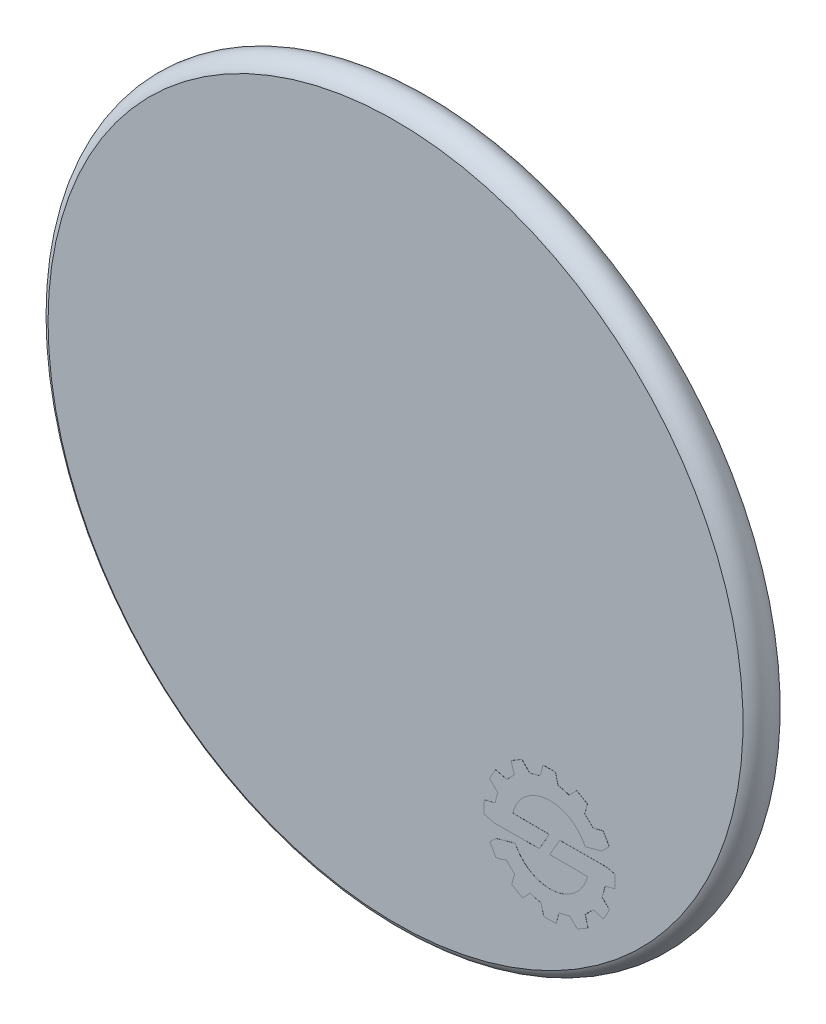
SolidWorks part; units mm, degrees
ref_plane "Front Plane" through (0, 0, 0) normal (0, 0, 1) x (1, 0, 0)
ref_plane "Top Plane" through (0, 0, 0) normal (0, 1, 0) x (1, 0, 0)
ref_plane "Right Plane" through (0, 0, 0) normal (1, 0, 0) x (0, 0, -1)
sketch "Sketch1" plane through (0, 0, 0) normal (0, 1, 0) x (1, 0, 0)
  line L0 (0, 0) -> (-40, 0)
  line L3 (-40, 0) -> (-42, 1.5)
  line L4 (0, 0) -> (0, -3)
  line L5 (0, -3) -> (-42, -3)
  line L6 (-42, -3) -> (-44.5, -3)
  line L8 (-44.5, 1.5) -> (-42, 1.5)
  arc A0 (-44.5, 1.5) -> (-44.5, -3) centre (-43.5625, -0.75) ccw
  dimension "D1" = 40
  dimension "D2" = 42
revolve "Revolve1" add sketch "Sketch1" angle 360 about L4
sketch "Sketch5" plane through (0, 0, 3) normal (0, 0, 1) x (1, 0, 0)
  line L0 (16.6947, -18.7297) -> (16.1934, -18.2222)
  line L1 (16.1934, -18.2222) -> (16.1083, -18.2709)
  line L2 (14.8898, -18.991) -> (14.8169, -19.0457)
  line L3 (14.8169, -19.0457) -> (14.8685, -19.2432)
  line L4 (15.1116, -20.0667) -> (15.221, -20.4222)
  line L5 (15.221, -20.4222) -> (14.8777, -20.7655)
  line L6 (12.1187, -22.2757) -> (12.0518, -22.4124)
  line L7 (12.0518, -22.4124) -> (12.3374, -22.6859)
  line L8 (12.1004, -26.8973) -> (12.617, -27.0189)
  line L9 (12.617, -27.0189) -> (15.4915, -27.0189)
  line L10 (24.1878, -23.6491) -> (24.2911, -23.8497)
  line L11 (24.2911, -23.8497) -> (24.4856, -23.798)
  line L12 (25.543, -23.5093) -> (26.3999, -23.2723)
  line L13 (26.3999, -23.2723) -> (26.886, -22.8014)
  line L14 (26.6186, -21.0056) -> (26.5609, -20.9326)
  line L15 (26.5609, -20.9326) -> (26.2145, -21.0329)
  line L16 (24.4734, -20.4404) -> (24.2364, -20.2277)
  line L17 (24.2364, -20.2277) -> (24.3914, -19.6808)
  line L18 (23.4221, -18.3013) -> (23.1942, -18.1706)
  line L19 (23.1942, -18.1706) -> (22.7202, -18.6659)
  line L20 (22.7202, -18.6659) -> (22.2462, -19.1612)
  line L21 (22.2462, -19.1612) -> (22.0669, -19.0943)
  line L22 (20.5294, -17.5963) -> (20.496, -17.4778)
  line L23 (20.496, -17.4778) -> (19.6938, -17.4778)
  line L24 (20.3805, -25.8885) -> (19.7515, -26.9885)
  line L25 (19.7515, -26.9885) -> (22.1641, -26.9885)
  line L26 (12.4438, -29.0486) -> (12.0822, -29.4102)
  line L27 (12.0822, -29.4102) -> (12.2189, -29.6351)
  line L28 (14.747, -30.8961) -> (15.2544, -31.4035)
  line L29 (15.2544, -31.4035) -> (15.1299, -31.8623)
  line L30 (16.1721, -33.4697) -> (16.2906, -33.5274)
  line L31 (16.2906, -33.5274) -> (16.4608, -33.3482)
  line L32 (16.9408, -32.8438) -> (17.2538, -32.5156)
  line L33 (17.2538, -32.5156) -> (17.5273, -32.6098)
  line L34 (20.3562, -34.2202) -> (20.5871, -34.2202)
  line L35 (20.5871, -34.2202) -> (20.7451, -33.567)
  line L36 (25.2057, -30.4403) -> (25.3029, -30.3218)
  line L37 (25.3029, -30.3218) -> (25.6007, -30.4069)
  line L38 (26.2692, -30.5892) -> (26.6399, -30.6894)
  line L39 (26.6399, -30.6894) -> (26.7888, -30.4281)
  line L40 (26.6916, -28.5928) -> (26.4485, -28.3649)
  line L41 (26.4485, -28.3649) -> (26.5731, -27.9882)
  line L42 (27.5089, -26.7606) -> (28.1166, -26.6087)
  line L43 (28.1166, -26.6087) -> (28.1166, -25.8034)
  line L44 (28.1166, -25.8034) -> (28.1166, -24.9982)
  line L45 (28.1166, -24.9982) -> (27.6153, -24.8706)
  line L46 (27.6153, -24.8706) -> (27.1139, -24.746)
  line L47 (27.1139, -24.746) -> (24.1209, -24.746)
  spline S0 degree 3 poles (18.8916, -17.4839) (18.8916, -17.49) (18.8126, -17.7999) (18.7184, -18.1767) knots 0 0 0 0 1 1 1 1
  spline S1 degree 3 poles (18.7184, -18.1767) (18.5239, -18.9424) (18.5756, -18.8603) (18.2262, -18.9393) knots 0 0 0 0 1 1 1 1
  spline S2 degree 3 poles (18.2262, -18.9393) (18.135, -18.9576) (17.8737, -19.0335) (17.6488, -19.1065) knots 0 0 0 0 1 1 1 1
  spline S3 degree 3 poles (17.6488, -19.1065) (17.424, -19.1794) (17.2295, -19.2402) (17.2174, -19.2402) knots 0 0 0 0 1 1 1 1
  spline S4 degree 3 poles (17.2174, -19.2402) (17.2052, -19.2402) (16.9682, -19.0123) (16.6947, -18.7297) knots 0 0 0 0 1 1 1 1
  spline S5 degree 3 poles (16.1083, -18.2709) (15.3881, -18.6871) (14.9476, -18.9485) (14.8898, -18.991) knots 0 0 0 0 1 1 1 1
  spline S6 degree 3 poles (14.8685, -19.2432) (14.9232, -19.4529) (14.9415, -19.5197) (15.1116, -20.0667) knots 0 0 0 0 1 1 1 1
  spline S7 degree 3 poles (14.8777, -20.7655) (14.6893, -20.9539) (14.4796, -21.1727) (14.4128, -21.2517) knots 0 0 0 0 1 1 1 1
  spline S8 degree 3 poles (14.4128, -21.2517) (14.3459, -21.3307) (14.27, -21.3975) (14.2456, -21.3975) knots 0 0 0 0 1 1 1 1
  spline S9 degree 3 poles (14.2456, -21.3975) (14.2213, -21.3975) (14.0573, -21.355) (13.881, -21.3064) knots 0 0 0 0 1 1 1 1
  spline S10 degree 3 poles (13.881, -21.3064) (13.2399, -21.121) (12.8418, -21.0268) (12.8175, -21.0511) knots 0 0 0 0 1 1 1 1
  spline S11 degree 3 poles (12.8175, -21.0511) (12.8054, -21.0663) (12.7324, -21.1879) (12.6595, -21.3216) knots 0 0 0 0 1 1 1 1
  spline S12 degree 3 poles (12.6595, -21.3216) (12.5836, -21.4553) (12.4468, -21.6953) (12.3557, -21.8533) knots 0 0 0 0 1 1 1 1
  spline S13 degree 3 poles (12.3557, -21.8533) (12.2645, -22.0113) (12.1582, -22.2028) (12.1187, -22.2757) knots 0 0 0 0 1 1 1 1
  spline S14 degree 3 poles (12.3374, -22.6859) (12.4924, -22.8378) (12.7324, -23.0687) (12.8722, -23.2024) knots 0 0 0 0 1 1 1 1
  spline S15 degree 3 poles (12.8722, -23.2024) (13.009, -23.3331) (13.1214, -23.4486) (13.1214, -23.4546) knots 0 0 0 0 1 1 1 1
  spline S16 degree 3 poles (13.1214, -23.4546) (13.1214, -23.4638) (13.0819, -23.5792) (13.0333, -23.716) knots 0 0 0 0 1 1 1 1
  spline S17 degree 3 poles (13.0333, -23.716) (12.9877, -23.8527) (12.9178, -24.1019) (12.8783, -24.269) knots 0 0 0 0 1 1 1 1
  spline S18 degree 3 poles (12.8783, -24.269) (12.8418, -24.4361) (12.8023, -24.6123) (12.7902, -24.6609) knots 0 0 0 0 1 1 1 1
  spline S19 degree 3 poles (12.7902, -24.6609) (12.7689, -24.7491) (12.7568, -24.7551) (12.3162, -24.8645) knots 0 0 0 0 1 1 1 1
  spline S20 degree 3 poles (12.3162, -24.8645) (12.064, -24.9253) (11.7571, -25.0013) (11.6325, -25.0316) knots 0 0 0 0 1 1 1 1
  spline S21 degree 3 poles (11.6325, -25.0316) (11.5079, -25.059) (11.3864, -25.0955) (11.3651, -25.1137) knots 0 0 0 0 1 1 1 1
  spline S22 degree 3 poles (11.3651, -25.1137) (11.3377, -25.135) (11.3286, -25.3234) (11.3317, -25.8916) knots 0 0 0 0 1 1 1 1
  spline S23 degree 3 poles (11.3317, -25.8916) (11.3317, -26.3018) (11.3469, -26.6603) (11.359, -26.6877) knots 0 0 0 0 1 1 1 1
  spline S24 degree 3 poles (11.359, -26.6877) (11.3742, -26.715) (11.4319, -26.7454) (11.4866, -26.7545) knots 0 0 0 0 1 1 1 1
  spline S25 degree 3 poles (11.4866, -26.7545) (11.5413, -26.7636) (11.8178, -26.8274) (12.1004, -26.8973) knots 0 0 0 0 1 1 1 1
  spline S26 degree 3 poles (15.4915, -27.0189) (17.7461, -27.0189) (18.3781, -27.0097) (18.4145, -26.9794) knots 0 0 0 0 1 1 1 1
  spline S27 degree 3 poles (18.4145, -26.9794) (18.4389, -26.9611) (18.5969, -26.7029) (18.764, -26.4112) knots 0 0 0 0 1 1 1 1
  spline S28 degree 3 poles (18.764, -26.4112) (18.9311, -26.1195) (19.2076, -25.6394) (19.3778, -25.3446) knots 0 0 0 0 1 1 1 1
  spline S29 degree 3 poles (19.3778, -25.3446) (19.5449, -25.0499) (19.6847, -24.7977) (19.6847, -24.7886) knots 0 0 0 0 1 1 1 1
  spline S30 degree 3 poles (19.6847, -24.7886) (19.6847, -24.7794) (18.6394, -24.7703) (17.3602, -24.7703) knots 0 0 0 0 1 1 1 1
  spline S31 degree 3 poles (17.3602, -24.7703) (15.139, -24.7703) (15.0357, -24.7673) (15.0357, -24.7156) knots 0 0 0 0 1 1 1 1
  spline S32 degree 3 poles (15.0357, -24.7156) (15.0357, -24.6458) (15.218, -24.1079) (15.3152, -23.8892) knots 0 0 0 0 1 1 1 1
  spline S33 degree 3 poles (15.3152, -23.8892) (16.1295, -22.0691) (18.0074, -20.8992) (19.9733, -20.9843) knots 0 0 0 0 1 1 1 1
  spline S34 degree 3 poles (19.9733, -20.9843) (21.4926, -21.0481) (22.7809, -21.7105) (23.7077, -22.8955) knots 0 0 0 0 1 1 1 1
  spline S35 degree 3 poles (23.7077, -22.8955) (23.8171, -23.0384) (23.9082, -23.1599) (23.9082, -23.169) knots 0 0 0 0 1 1 1 1
  spline S36 degree 3 poles (23.9082, -23.169) (23.9082, -23.1781) (23.9478, -23.245) (23.9964, -23.3179) knots 0 0 0 0 1 1 1 1
  spline S37 degree 3 poles (23.9964, -23.3179) (24.0419, -23.3908) (24.1301, -23.5397) (24.1878, -23.6491) knots 0 0 0 0 1 1 1 1
  spline S38 degree 3 poles (24.4856, -23.798) (24.595, -23.7706) (25.069, -23.64) (25.543, -23.5093) knots 0 0 0 0 1 1 1 1
  spline S39 degree 3 poles (26.886, -22.8014) (27.1534, -22.54) (27.3722, -22.3182) (27.3722, -22.3061) knots 0 0 0 0 1 1 1 1
  spline S40 degree 3 poles (27.3722, -22.3061) (27.3722, -22.2909) (27.2324, -22.0447) (27.0653, -21.7561) knots 0 0 0 0 1 1 1 1
  spline S41 degree 3 poles (27.0653, -21.7561) (26.8951, -21.4674) (26.7371, -21.197) (26.7159, -21.1545) knots 0 0 0 0 1 1 1 1
  spline S42 degree 3 poles (26.7159, -21.1545) (26.6916, -21.1119) (26.649, -21.0451) (26.6186, -21.0056) knots 0 0 0 0 1 1 1 1
  spline S43 degree 3 poles (26.2145, -21.0329) (26.0231, -21.0846) (25.7648, -21.1636) (25.6372, -21.2031) knots 0 0 0 0 1 1 1 1
  spline S44 degree 3 poles (25.6372, -21.2031) (25.5096, -21.2426) (25.385, -21.276) (25.3576, -21.276) knots 0 0 0 0 1 1 1 1
  spline S45 degree 3 poles (25.3576, -21.276) (25.3333, -21.276) (25.2513, -21.2122) (25.1784, -21.1332) knots 0 0 0 0 1 1 1 1
  spline S46 degree 3 poles (25.1784, -21.1332) (24.9596, -20.8962) (24.7256, -20.6652) (24.4734, -20.4404) knots 0 0 0 0 1 1 1 1
  spline S47 degree 3 poles (24.3914, -19.6808) (24.6071, -18.912) (24.6041, -18.9637) (24.4643, -18.8907) knots 0 0 0 0 1 1 1 1
  spline S48 degree 3 poles (24.4643, -18.8907) (24.4005, -18.8573) (24.1908, -18.7388) (23.9994, -18.6294) knots 0 0 0 0 1 1 1 1
  spline S49 degree 3 poles (23.9994, -18.6294) (23.808, -18.52) (23.5467, -18.3711) (23.4221, -18.3013) knots 0 0 0 0 1 1 1 1
  spline S50 degree 3 poles (22.0669, -19.0943) (21.8299, -19.0092) (21.3467, -18.8847) (21.1584, -18.8603) knots 0 0 0 0 1 1 1 1
  spline S51 degree 3 poles (21.1584, -18.8603) (20.815, -18.8148) (20.8363, -18.8421) (20.6935, -18.3043) knots 0 0 0 0 1 1 1 1
  spline S52 degree 3 poles (20.6935, -18.3043) (20.6236, -18.0399) (20.5658, -17.7999) (20.5658, -17.7695) knots 0 0 0 0 1 1 1 1
  spline S53 degree 3 poles (20.5658, -17.7695) (20.5658, -17.7391) (20.5506, -17.6601) (20.5294, -17.5963) knots 0 0 0 0 1 1 1 1
  spline S54 degree 3 poles (19.6938, -17.4778) (19.2562, -17.4778) (18.8946, -17.4808) (18.8916, -17.4839) knots 0 0 0 0 1 1 1 1
  spline S55 degree 3 poles (21.0702, -24.7673) (21.0368, -24.7794) (20.7542, -25.2413) (20.3805, -25.8885) knots 0 0 0 0 1 1 1 1
  spline S56 degree 3 poles (22.1641, -26.9885) (24.1453, -26.9885) (24.5767, -26.9946) (24.5767, -27.028) knots 0 0 0 0 1 1 1 1
  spline S57 degree 3 poles (24.5767, -27.028) (24.5767, -27.0523) (24.5433, -27.1829) (24.5008, -27.3197) knots 0 0 0 0 1 1 1 1
  spline S58 degree 3 poles (24.5008, -27.3197) (24.285, -28.0398) (23.8171, -28.8116) (23.2762, -29.3494) knots 0 0 0 0 1 1 1 1
  spline S59 degree 3 poles (23.2762, -29.3494) (22.5774, -30.0361) (21.8238, -30.4433) (20.8089, -30.6834) knots 0 0 0 0 1 1 1 1
  spline S60 degree 3 poles (20.8089, -30.6834) (20.3228, -30.7958) (19.5631, -30.814) (19.0466, -30.7259) knots 0 0 0 0 1 1 1 1
  spline S61 degree 3 poles (19.0466, -30.7259) (17.6124, -30.4767) (16.5306, -29.787) (15.7011, -28.5837) knots 0 0 0 0 1 1 1 1
  spline S62 degree 3 poles (15.7011, -28.5837) (15.6434, -28.4986) (15.5401, -28.3254) (15.4763, -28.1978) knots 0 0 0 0 1 1 1 1
  spline S63 degree 3 poles (15.4763, -28.1978) (15.4094, -28.0672) (15.3395, -27.9608) (15.3243, -27.9608) knots 0 0 0 0 1 1 1 1
  spline S64 degree 3 poles (15.3243, -27.9608) (15.3061, -27.9608) (15.1754, -27.9942) (15.0357, -28.0337) knots 0 0 0 0 1 1 1 1
  spline S65 degree 3 poles (15.0357, -28.0337) (14.8929, -28.0763) (14.3672, -28.2191) (13.8658, -28.3558) knots 0 0 0 0 1 1 1 1
  spline S66 degree 3 poles (13.8658, -28.3558) (13.3645, -28.4956) (12.9208, -28.6232) (12.8783, -28.6445) knots 0 0 0 0 1 1 1 1
  spline S67 degree 3 poles (12.8783, -28.6445) (12.8358, -28.6688) (12.6413, -28.8481) (12.4438, -29.0486) knots 0 0 0 0 1 1 1 1
  spline S68 degree 3 poles (12.2189, -29.6351) (12.3496, -29.8538) (12.5289, -30.1577) (12.6352, -30.3461) knots 0 0 0 0 1 1 1 1
  spline S69 degree 3 poles (12.6352, -30.3461) (12.6626, -30.3947) (12.7324, -30.5102) (12.7871, -30.6013) knots 0 0 0 0 1 1 1 1
  spline S70 degree 3 poles (12.7871, -30.6013) (12.8844, -30.7593) (12.8904, -30.7624) (13.0029, -30.7441) knots 0 0 0 0 1 1 1 1
  spline S71 degree 3 poles (13.0029, -30.7441) (13.0667, -30.735) (13.2247, -30.6925) (13.3553, -30.653) knots 0 0 0 0 1 1 1 1
  spline S72 degree 3 poles (13.3553, -30.653) (13.486, -30.6104) (13.7261, -30.5375) (13.8901, -30.4859) knots 0 0 0 0 1 1 1 1
  spline S73 degree 3 poles (13.8901, -30.4859) (14.0542, -30.4342) (14.2001, -30.3917) (14.2153, -30.3917) knots 0 0 0 0 1 1 1 1
  spline S74 degree 3 poles (14.2153, -30.3917) (14.2305, -30.3917) (14.4705, -30.6196) (14.747, -30.8961) knots 0 0 0 0 1 1 1 1
  spline S75 degree 3 poles (15.1299, -31.8623) (15.06, -32.1145) (14.9749, -32.4062) (14.9445, -32.5126) knots 0 0 0 0 1 1 1 1
  spline S76 degree 3 poles (14.9445, -32.5126) (14.8898, -32.6949) (14.8898, -32.7921) (14.9476, -32.7921) knots 0 0 0 0 1 1 1 1
  spline S77 degree 3 poles (14.9476, -32.7921) (14.9627, -32.7921) (15.0387, -32.8316) (15.1177, -32.8772) knots 0 0 0 0 1 1 1 1
  spline S78 degree 3 poles (15.1177, -32.8772) (15.3729, -33.0322) (16.0505, -33.4089) (16.1721, -33.4697) knots 0 0 0 0 1 1 1 1
  spline S79 degree 3 poles (16.4608, -33.3482) (16.5549, -33.2509) (16.7707, -33.023) (16.9408, -32.8438) knots 0 0 0 0 1 1 1 1
  spline S80 degree 3 poles (17.5273, -32.6098) (17.7795, -32.6949) (18.2687, -32.8195) (18.5361, -32.865) knots 0 0 0 0 1 1 1 1
  spline S81 degree 3 poles (18.5361, -32.865) (18.6303, -32.8833) (18.6485, -32.8985) (18.6667, -32.9835) knots 0 0 0 0 1 1 1 1
  spline S82 degree 3 poles (18.6667, -32.9835) (18.7123, -33.2145) (18.9676, -34.1777) (18.9919, -34.2081) knots 0 0 0 0 1 1 1 1
  spline S83 degree 3 poles (18.9919, -34.2081) (19.0101, -34.2324) (19.1833, -34.2415) (19.5722, -34.2324) knots 0 0 0 0 1 1 1 1
  spline S84 degree 3 poles (19.5722, -34.2324) (19.8761, -34.2263) (20.2286, -34.2233) (20.3562, -34.2202) knots 0 0 0 0 1 1 1 1
  spline S85 degree 3 poles (20.7451, -33.567) (20.8332, -33.2084) (20.9244, -32.9015) (20.9457, -32.8833) knots 0 0 0 0 1 1 1 1
  spline S86 degree 3 poles (20.9457, -32.8833) (20.9639, -32.8681) (21.055, -32.8377) (21.1462, -32.8225) knots 0 0 0 0 1 1 1 1
  spline S87 degree 3 poles (21.1462, -32.8225) (21.3802, -32.78) (22.0942, -32.5764) (22.1307, -32.546) knots 0 0 0 0 1 1 1 1
  spline S88 degree 3 poles (22.1307, -32.546) (22.1459, -32.5308) (22.1945, -32.5186) (22.2431, -32.5186) knots 0 0 0 0 1 1 1 1
  spline S89 degree 3 poles (22.2431, -32.5186) (22.31, -32.5186) (22.4133, -32.6068) (22.787, -32.9896) knots 0 0 0 0 1 1 1 1
  spline S90 degree 3 poles (22.787, -32.9896) (23.0423, -33.2479) (23.2732, -33.4606) (23.2975, -33.4606) knots 0 0 0 0 1 1 1 1
  spline S91 degree 3 poles (23.2975, -33.4606) (23.3248, -33.4606) (23.3735, -33.4424) (23.4069, -33.4181) knots 0 0 0 0 1 1 1 1
  spline S92 degree 3 poles (23.4069, -33.4181) (23.4403, -33.3968) (23.5163, -33.3512) (23.574, -33.3178) knots 0 0 0 0 1 1 1 1
  spline S93 degree 3 poles (23.574, -33.3178) (23.6895, -33.2509) (23.9721, -33.0869) (24.1361, -32.9896) knots 0 0 0 0 1 1 1 1
  spline S94 degree 3 poles (24.1361, -32.9896) (24.1939, -32.9562) (24.3306, -32.8772) (24.44, -32.8134) knots 0 0 0 0 1 1 1 1
  spline S95 degree 3 poles (24.44, -32.8134) (24.6648, -32.6827) (24.6679, -32.6706) (24.5767, -32.3698) knots 0 0 0 0 1 1 1 1
  spline S96 degree 3 poles (24.5767, -32.3698) (24.3944, -31.762) (24.3033, -31.44) (24.3033, -31.3913) knots 0 0 0 0 1 1 1 1
  spline S97 degree 3 poles (24.3033, -31.3913) (24.3033, -31.364) (24.3549, -31.2941) (24.4187, -31.2364) knots 0 0 0 0 1 1 1 1
  spline S98 degree 3 poles (24.4187, -31.2364) (24.598, -31.0753) (25.0994, -30.5709) (25.2057, -30.4403) knots 0 0 0 0 1 1 1 1
  spline S99 degree 3 poles (25.6007, -30.4069) (25.7648, -30.4524) (26.0656, -30.5345) (26.2692, -30.5892) knots 0 0 0 0 1 1 1 1
  spline S100 degree 3 poles (26.7888, -30.4281) (27.2871, -29.5439) (27.4026, -29.3312) (27.4026, -29.3039) knots 0 0 0 0 1 1 1 1
  spline S101 degree 3 poles (27.4026, -29.3039) (27.4026, -29.2765) (27.2659, -29.1367) (26.6916, -28.5928) knots 0 0 0 0 1 1 1 1
  spline S102 degree 3 poles (26.5731, -27.9882) (26.6429, -27.7815) (26.7311, -27.4595) (26.7675, -27.2771) knots 0 0 0 0 1 1 1 1
  spline S103 degree 3 poles (26.7675, -27.2771) (26.807, -27.0918) (26.8526, -26.9368) (26.8708, -26.9277) knots 0 0 0 0 1 1 1 1
  spline S104 degree 3 poles (26.8708, -26.9277) (26.886, -26.9216) (27.1747, -26.8457) (27.5089, -26.7606) knots 0 0 0 0 1 1 1 1
  spline S105 degree 3 poles (24.1209, -24.746) (22.4741, -24.746) (21.1006, -24.7551) (21.0702, -24.7673) knots 0 0 0 0 1 1 1 1
extrude "Boss-Extrude2" add sketch "Sketch5" along normal blind 0.01
sketch "Sketch6" plane through (0, 0, 0) normal (0, 0, -1) x (-1, 0, 0)
  line L0 (-1.1362, 11.5137) -> (-1.1362, 13.4643)
  line L1 (-1.1362, 13.4643) -> (-2.3103, 14.43)
  line L2 (-8.7111, 20.3952) -> (-8.7111, 18.1417)
  line L3 (-8.7111, 18.1417) -> (-7.1203, 16.8351)
  line L4 (-3.901, 14.2028) -> (-2.2724, 12.8772)
  line L5 (-2.2724, 12.8772) -> (-2.2724, 11.2297)
  line L6 (-2.2724, 11.2297) -> (-2.2724, 9.5632)
  line L7 (-2.2724, 9.5632) -> (-4.3555, 9.5632)
  line L8 (-4.3555, 9.5632) -> (-6.4386, 9.5632)
  line L9 (-6.4386, 9.5632) -> (-6.4386, 10.5669)
  line L10 (-6.4386, 10.5669) -> (-6.4386, 11.5706)
  line L11 (-6.4386, 11.5706) -> (-9.3739, 13.5589)
  line L12 (-9.3739, 13.5589) -> (-12.3091, 15.5284)
  line L13 (-12.3091, 15.5284) -> (-12.3091, 16.7972)
  line L14 (-13.4453, 16.5889) -> (-13.4453, 14.9413)
  line L15 (-13.4453, 14.9413) -> (-10.6426, 13.0666)
  line L16 (-10.0745, 8.0861) -> (-11.0782, 8.1429)
  line L17 (-11.0782, 8.1429) -> (-13.0476, 11.0403)
  line L18 (-13.0476, 11.0403) -> (-15.0171, 13.9187)
  line L19 (-15.0171, 13.9187) -> (-16.5889, 13.9187)
  line L20 (-10.3018, 6.912) -> (-9.0898, 6.912)
  line L21 (-9.0898, 6.912) -> (-9.0898, 5.0183)
  line L22 (-9.0898, 5.0183) -> (-9.0898, 3.1246)
  line L23 (-9.0898, 3.1246) -> (-10.9646, 3.1246)
  line L24 (-10.9646, 3.1246) -> (-12.8204, 3.1246)
  line L25 (-12.8204, 3.1246) -> (-15.2633, 6.0788)
  line L26 (-20.6793, 8.427) -> (-18.653, 8.427)
  line L27 (-18.653, 8.427) -> (-16.0397, 5.2077)
  line L28 (-16.0397, 5.2077) -> (-13.4264, 1.9884)
  line L29 (-13.4264, 1.9884) -> (-11.2486, 1.9884)
  line L30 (-11.2486, 1.9884) -> (-9.0898, 1.9884)
  line L31 (-9.0898, 1.9884) -> (-9.0898, 1.515)
  line L32 (-9.0898, 1.515) -> (-9.0898, 1.0415)
  line L33 (-9.0898, 1.0415) -> (-16.9297, 1.0415)
  line L34 (-16.9297, 1.0415) -> (-24.7886, 1.0415)
  line L35 (-24.7886, 1.0415) -> (-24.9212, 1.4771)
  line L36 (-16.9297, -0.0947) -> (-9.0709, -0.0947)
  line L37 (-9.0709, -0.0947) -> (-9.1277, -0.606)
  line L38 (-9.1277, -0.606) -> (-9.1845, -1.1362)
  line L39 (-9.1845, -1.1362) -> (-10.9456, -1.0605)
  line L40 (-17.0055, -6.2114) -> (-18.0281, -7.4801)
  line L41 (-18.0281, -7.4801) -> (-20.0354, -7.4801)
  line L42 (-20.0354, -7.4801) -> (-22.0617, -7.4801)
  line L43 (-22.0617, -7.4801) -> (-22.3457, -6.8552)
  line L44 (-22.3647, -9.3739) -> (-21.9481, -8.6164)
  line L45 (-21.9481, -8.6164) -> (-19.7135, -8.6164)
  line L46 (-19.7135, -8.6164) -> (-17.4789, -8.6164)
  line L47 (-17.4789, -8.6164) -> (-15.9829, -6.7795)
  line L48 (-13.3885, -3.6549) -> (-12.3091, -2.3293)
  line L49 (-12.3091, -2.3293) -> (-10.7373, -2.3293)
  line L50 (-10.7373, -2.3293) -> (-9.1845, -2.3293)
  line L51 (-9.1845, -2.3293) -> (-9.1845, -4.204)
  line L52 (-9.1845, -4.204) -> (-9.1845, -6.0599)
  line L53 (-9.1845, -6.0599) -> (-10.1313, -6.0599)
  line L54 (-10.1313, -6.0599) -> (-11.0782, -6.0599)
  line L55 (-11.0782, -6.0599) -> (-13.0287, -8.9383)
  line L56 (-13.0287, -8.9383) -> (-14.9792, -11.8357)
  line L57 (-14.9792, -11.8357) -> (-16.2669, -11.8357)
  line L58 (-7.6695, -9.4307) -> (-10.5101, -12.1008)
  line L59 (-10.5101, -12.1008) -> (-13.3506, -14.0324)
  line L60 (-13.3506, -14.0324) -> (-13.4074, -15.6799)
  line L61 (-11.6463, -17.5736) -> (-12.3091, -15.9829)
  line L62 (-12.3091, -15.9829) -> (-12.3091, -14.6952)
  line L63 (-12.3091, -14.6952) -> (-10.2639, -13.3317)
  line L64 (-6.4386, -9.639) -> (-6.4386, -8.6164)
  line L65 (-6.4386, -8.6164) -> (-4.6396, -8.6164)
  line L66 (-4.6396, -8.6164) -> (-2.8406, -8.6164)
  line L67 (-2.8406, -8.6164) -> (-2.8406, -10.3586)
  line L68 (-2.8406, -10.3586) -> (-2.8406, -12.1197)
  line L69 (-2.8406, -12.1197) -> (-4.9615, -13.8241)
  line L70 (-8.0672, -16.3806) -> (-9.0898, -17.2138)
  line L71 (-9.0898, -17.2138) -> (-9.0898, -19.4105)
  line L72 (-9.0898, -19.4105) -> (-9.0898, -21.6261)
  line L73 (-9.0898, -21.6261) -> (-9.7905, -22.0806)
  line L74 (-7.9536, -19.7892) -> (-7.9536, -17.763)
  line L75 (-7.9536, -17.763) -> (-5.0941, -15.4148)
  line L76 (-1.515, -10.5858) -> (-1.515, -8.6164)
  line L77 (-1.515, -8.6164) -> (-1.0415, -8.6164)
  line L78 (-1.0415, -8.6164) -> (-0.5681, -8.6164)
  line L79 (-0.5681, -8.6164) -> (-0.5681, -16.4753)
  line L80 (1.0983, -10.6616) -> (1.1552, -12.5742)
  line L81 (1.1552, -12.5742) -> (2.4997, -13.6726)
  line L82 (7.4801, -19.6567) -> (7.5748, -21.664)
  line L83 (7.5748, -21.664) -> (6.912, -21.9859)
  line L84 (9.2792, -22.0238) -> (8.6542, -21.7019)
  line L85 (8.6542, -21.7019) -> (8.6732, -19.5241)
  line L86 (8.6732, -19.5241) -> (8.6921, -17.3274)
  line L87 (8.6921, -17.3274) -> (7.6127, -16.3995)
  line L88 (4.4502, -13.7862) -> (2.3671, -12.1008)
  line L89 (2.3671, -12.1008) -> (2.3103, -10.3586)
  line L90 (2.3103, -10.3586) -> (2.2535, -8.6164)
  line L91 (2.2535, -8.6164) -> (4.3555, -8.6164)
  line L92 (4.3555, -8.6164) -> (6.4386, -8.6164)
  line L93 (6.4386, -8.6164) -> (6.4386, -9.639)
  line L94 (6.4386, -9.639) -> (6.4386, -10.6805)
  line L95 (6.4386, -10.6805) -> (9.3739, -12.6878)
  line L96 (9.3739, -12.6878) -> (12.3091, -14.7141)
  line L97 (12.3091, -14.7141) -> (12.3091, -15.9829)
  line L98 (12.3091, -15.9829) -> (11.6463, -17.5736)
  line L99 (14.1081, -17.5925) -> (13.4643, -17.2517)
  line L100 (13.4643, -17.2517) -> (13.4074, -15.642)
  line L101 (13.4074, -15.642) -> (13.3506, -14.0134)
  line L102 (13.3506, -14.0134) -> (10.5101, -12.0819)
  line L103 (12.6878, -10.3775) -> (14.43, -12.9719)
  line L104 (14.43, -12.9719) -> (16.0208, -12.9719)
  line L105 (17.8577, -11.1729) -> (16.3048, -11.8357)
  line L106 (16.3048, -11.8357) -> (15.055, -11.8167)
  line L107 (15.055, -11.8167) -> (13.2749, -9.1655)
  line L108 (9.1277, -4.1472) -> (9.1845, -2.3293)
  line L109 (9.1845, -2.3293) -> (10.7563, -2.3293)
  line L110 (10.7563, -2.3293) -> (12.328, -2.3293)
  line L111 (12.328, -2.3293) -> (14.8845, -5.4728)
  line L112 (14.8845, -5.4728) -> (17.441, -8.6164)
  line L113 (17.441, -8.6164) -> (19.6946, -8.6164)
  line L114 (19.6946, -8.6164) -> (21.9291, -8.6164)
  line L115 (21.9291, -8.6164) -> (22.4215, -9.4496)
  line L116 (22.3457, -6.8552) -> (22.0617, -7.4801)
  line L117 (22.0617, -7.4801) -> (20.0544, -7.4801)
  line L118 (20.0544, -7.4801) -> (18.047, -7.4801)
  line L119 (18.047, -7.4801) -> (16.0776, -5.0941)
  line L120 (10.8888, -1.0605) -> (9.1845, -1.0983)
  line L121 (9.1845, -1.0983) -> (9.1277, -0.587)
  line L122 (9.1277, -0.587) -> (9.0709, -0.0947)
  line L123 (9.0709, -0.0947) -> (16.9297, -0.0947)
  line L124 (16.9487, 1.0415) -> (9.0898, 1.0415)
  line L125 (9.0898, 1.0415) -> (9.0898, 1.515)
  line L126 (9.0898, 1.515) -> (9.0898, 1.9884)
  line L127 (9.0898, 1.9884) -> (11.2486, 1.9884)
  line L128 (11.2486, 1.9884) -> (13.4074, 1.9884)
  line L129 (13.4074, 1.9884) -> (16.0397, 5.2077)
  line L130 (16.0397, 5.2077) -> (18.653, 8.427)
  line L131 (18.653, 8.427) -> (20.6982, 8.427)
  line L132 (20.3763, 9.5632) -> (18.0281, 9.5632)
  line L133 (18.0281, 9.5632) -> (17.4789, 8.8436)
  line L134 (14.8845, 5.6243) -> (12.8204, 3.1246)
  line L135 (12.8204, 3.1246) -> (10.9456, 3.1246)
  line L136 (10.9456, 3.1246) -> (9.0898, 3.1246)
  line L137 (9.0898, 3.1246) -> (9.0898, 5.0183)
  line L138 (9.0898, 5.0183) -> (9.0898, 6.912)
  line L139 (9.0898, 6.912) -> (10.3775, 6.912)
  line L140 (10.3775, 6.912) -> (11.6463, 6.912)
  line L141 (11.6463, 6.912) -> (13.54, 9.7337)
  line L142 (16.5699, 13.9187) -> (14.9792, 13.9187)
  line L143 (14.9792, 13.9187) -> (13.0287, 11.0403)
  line L144 (13.0287, 11.0403) -> (11.0592, 8.1429)
  line L145 (11.0592, 8.1429) -> (10.0745, 8.0861)
  line L146 (7.6316, 10.2828) -> (7.5938, 11.0214)
  line L147 (7.5938, 11.0214) -> (10.5101, 12.9908)
  line L148 (10.5101, 12.9908) -> (13.4453, 14.9603)
  line L149 (13.4453, 14.9603) -> (13.4453, 16.5889)
  line L150 (13.4453, 16.5889) -> (13.4453, 18.1985)
  line L151 (13.4453, 18.1985) -> (14.1271, 18.5205)
  line L152 (12.2712, 16.8161) -> (12.2144, 15.5473)
  line L153 (12.2144, 15.5473) -> (9.336, 13.5779)
  line L154 (9.336, 13.5779) -> (6.4386, 11.6274)
  line L155 (6.4386, 11.6274) -> (6.4386, 10.5858)
  line L156 (6.4386, 10.5858) -> (6.4386, 9.5443)
  line L157 (6.4386, 9.5443) -> (4.6017, 9.6011)
  line L158 (4.6017, 9.6011) -> (2.7459, 9.6579)
  line L159 (2.7459, 9.6579) -> (2.7459, 11.2676)
  line L160 (2.7459, 11.2676) -> (2.7459, 12.8583)
  line L161 (2.7459, 12.8583) -> (5.8705, 15.4337)
  line L162 (5.8705, 15.4337) -> (8.9951, 18.0092)
  line L163 (8.9951, 18.0092) -> (9.0898, 20.3195)
  line L164 (9.0898, 20.3195) -> (9.1845, 22.6298)
  line L165 (9.1845, 22.6298) -> (9.8473, 22.9707)
  line L166 (3.5412, 15.055) -> (1.5339, 13.4453)
  line L167 (1.5339, 13.4453) -> (1.5339, 11.5137)
  line L168 (1.5339, 11.5137) -> (1.0415, 9.5632)
  line L169 (1.0415, 9.5632) -> (0.5681, 9.5632)
  line L170 (0.5681, 9.5632) -> (0.5681, 17.2327)
  line L171 (0.5681, 17.2327) -> (0.5681, 24.9022)
  line L172 (0.5681, 24.9022) -> (1.0226, 25.0159)
  line L173 (6.7795, 0.3598) -> (6.7227, -6.2492)
  line L174 (6.7227, -6.2492) -> (0.2272, -6.3439)
  line L175 (-4.507, 0) -> (-4.4502, -3.9768)
  line L176 (-4.4502, -3.9768) -> (0, -3.9768)
  line L177 (0, -3.9768) -> (4.4502, -3.9768)
  line L178 (4.4502, -3.9768) -> (4.507, 0)
  line L179 (4.4502, 4.4123) -> (4.3555, 4.829)
  line L180 (4.3555, 4.829) -> (0, 4.829)
  line L181 (0, 4.829) -> (-4.3555, 4.829)
  line L182 (-4.3555, 4.829) -> (-4.4502, 4.3934)
  spline S0 degree 3 poles (-1.4203, 29.8638) (-2.1778, 29.3903) (-2.3861, 29.1063) (-2.6323, 28.2162) knots 0 0 0 0 1 1 1 1
  spline S1 degree 3 poles (-2.6323, 28.2162) (-2.7837, 27.6671) (-2.7648, 27.2694) (-2.6133, 26.7391) knots 0 0 0 0 1 1 1 1
  spline S2 degree 3 poles (-2.6133, 26.7391) (-2.3861, 26.0006) (-1.3445, 24.9022) (-0.8522, 24.9022) knots 0 0 0 0 1 1 1 1
  spline S3 degree 3 poles (-0.8522, 24.9022) (-0.606, 24.9022) (-0.5681, 23.8418) (-0.5681, 17.2327) knots 0 0 0 0 1 1 1 1
  spline S4 degree 3 poles (-0.5681, 17.2327) (-0.5681, 10.5479) (-0.606, 9.5632) (-0.8522, 9.5632) knots 0 0 0 0 1 1 1 1
  spline S5 degree 3 poles (-0.8522, 9.5632) (-1.0794, 9.5632) (-1.1362, 9.9041) (-1.1362, 11.5137) knots 0 0 0 0 1 1 1 1
  spline S6 degree 3 poles (-2.3103, 14.43) (-2.9731, 14.9603) (-4.2608, 16.0018) (-5.2077, 16.7593) knots 0 0 0 0 1 1 1 1
  spline S7 degree 3 poles (-5.2077, 16.7593) (-7.6127, 18.6909) (-7.537, 18.5773) (-7.537, 20.3952) knots 0 0 0 0 1 1 1 1
  spline S8 degree 3 poles (-7.537, 20.3952) (-7.537, 22.1185) (-7.3476, 22.8192) (-6.931, 22.8192) knots 0 0 0 0 1 1 1 1
  spline S9 degree 3 poles (-6.931, 22.8192) (-6.5712, 22.8192) (-5.5296, 24.0311) (-5.3781, 24.6371) knots 0 0 0 0 1 1 1 1
  spline S10 degree 3 poles (-5.3781, 24.6371) (-4.7721, 27.0611) (-7.6316, 28.9927) (-9.6768, 27.5345) knots 0 0 0 0 1 1 1 1
  spline S11 degree 3 poles (-9.6768, 27.5345) (-10.6237, 26.8717) (-11.0782, 25.2431) (-10.5858, 24.2773) knots 0 0 0 0 1 1 1 1
  spline S12 degree 3 poles (-10.5858, 24.2773) (-10.2639, 23.6524) (-9.62, 22.9896) (-9.1277, 22.8002) knots 0 0 0 0 1 1 1 1
  spline S13 degree 3 poles (-9.1277, 22.8002) (-8.73, 22.6487) (-8.7111, 22.5541) (-8.7111, 20.3952) knots 0 0 0 0 1 1 1 1
  spline S14 degree 3 poles (-7.1203, 16.8351) (-6.2492, 16.1154) (-4.81, 14.9413) (-3.901, 14.2028) knots 0 0 0 0 1 1 1 1
  spline S15 degree 3 poles (-12.3091, 16.7972) (-12.3091, 18.0092) (-12.2712, 18.0849) (-11.7789, 18.35) knots 0 0 0 0 1 1 1 1
  spline S16 degree 3 poles (-11.7789, 18.35) (-10.7941, 18.8613) (-10.3586, 19.5241) (-10.2639, 20.6225) knots 0 0 0 0 1 1 1 1
  spline S17 degree 3 poles (-10.2639, 20.6225) (-10.1881, 21.6072) (-10.2071, 21.6829) (-10.9267, 22.4404) knots 0 0 0 0 1 1 1 1
  spline S18 degree 3 poles (-10.9267, 22.4404) (-11.5706, 23.1411) (-11.7978, 23.2547) (-12.6121, 23.3305) knots 0 0 0 0 1 1 1 1
  spline S19 degree 3 poles (-12.6121, 23.3305) (-14.2407, 23.463) (-15.4148, 22.3836) (-15.4148, 20.7361) knots 0 0 0 0 1 1 1 1
  spline S20 degree 3 poles (-15.4148, 20.7361) (-15.4148, 19.6756) (-14.6952, 18.5394) (-13.9187, 18.35) knots 0 0 0 0 1 1 1 1
  spline S21 degree 3 poles (-13.9187, 18.35) (-13.4643, 18.2364) (-13.4453, 18.1796) (-13.4453, 16.5889) knots 0 0 0 0 1 1 1 1
  spline S22 degree 3 poles (-10.6426, 13.0666) (-9.1087, 12.025) (-7.821, 11.1539) (-7.7831, 11.1161) knots 0 0 0 0 1 1 1 1
  spline S23 degree 3 poles (-7.7831, 11.1161) (-7.7263, 11.0971) (-7.6695, 10.7184) (-7.6506, 10.3207) knots 0 0 0 0 1 1 1 1
  spline S24 degree 3 poles (-7.6506, 10.3207) (-7.6316, 9.62) (-7.6695, 9.5632) (-8.124, 9.5632) knots 0 0 0 0 1 1 1 1
  spline S25 degree 3 poles (-8.124, 9.5632) (-8.7868, 9.5632) (-9.0898, 9.2413) (-9.0898, 8.5596) knots 0 0 0 0 1 1 1 1
  spline S26 degree 3 poles (-9.0898, 8.5596) (-9.0898, 8.0293) (-9.1087, 8.0293) (-10.0745, 8.0861) knots 0 0 0 0 1 1 1 1
  spline S27 degree 3 poles (-16.5889, 13.9187) (-18.1417, 13.9187) (-18.1796, 13.9187) (-18.4636, 14.4679) knots 0 0 0 0 1 1 1 1
  spline S28 degree 3 poles (-18.4636, 14.4679) (-18.9181, 15.358) (-19.7135, 15.8125) (-20.8118, 15.8125) knots 0 0 0 0 1 1 1 1
  spline S29 degree 3 poles (-20.8118, 15.8125) (-23.2358, 15.8125) (-24.2773, 12.8961) (-22.4215, 11.2865) knots 0 0 0 0 1 1 1 1
  spline S30 degree 3 poles (-22.4215, 11.2865) (-21.8913, 10.8131) (-21.6072, 10.6994) (-20.8687, 10.6994) knots 0 0 0 0 1 1 1 1
  spline S31 degree 3 poles (-20.8687, 10.6994) (-19.8082, 10.6994) (-18.8992, 11.1918) (-18.4826, 12.0061) knots 0 0 0 0 1 1 1 1
  spline S32 degree 3 poles (-18.4826, 12.0061) (-18.3121, 12.3091) (-18.0092, 12.6121) (-17.8008, 12.6878) knots 0 0 0 0 1 1 1 1
  spline S33 degree 3 poles (-17.8008, 12.6878) (-17.4789, 12.7825) (-15.5095, 12.6689) (-15.4337, 12.5363) knots 0 0 0 0 1 1 1 1
  spline S34 degree 3 poles (-15.4337, 12.5363) (-15.2065, 12.1387) (-12.4795, 8.1429) (-12.0629, 7.6316) knots 0 0 0 0 1 1 1 1
  spline S35 degree 3 poles (-12.0629, 7.6316) (-11.5327, 6.931) (-11.4759, 6.912) (-10.3018, 6.912) knots 0 0 0 0 1 1 1 1
  spline S36 degree 3 poles (-15.2633, 6.0788) (-16.6078, 7.7074) (-17.7819, 9.1466) (-17.8577, 9.2981) knots 0 0 0 0 1 1 1 1
  spline S37 degree 3 poles (-17.8577, 9.2981) (-17.9713, 9.5064) (-18.5394, 9.5632) (-20.3574, 9.5632) knots 0 0 0 0 1 1 1 1
  spline S38 degree 3 poles (-20.3574, 9.5632) (-22.3268, 9.5632) (-22.7245, 9.6011) (-22.7245, 9.8473) knots 0 0 0 0 1 1 1 1
  spline S39 degree 3 poles (-22.7245, 9.8473) (-22.7245, 9.9988) (-23.0654, 10.4722) (-23.482, 10.8888) knots 0 0 0 0 1 1 1 1
  spline S40 degree 3 poles (-23.482, 10.8888) (-24.1637, 11.5706) (-24.3341, 11.6463) (-25.1863, 11.6463) knots 0 0 0 0 1 1 1 1
  spline S41 degree 3 poles (-25.1863, 11.6463) (-26.9853, 11.6463) (-28.0269, 10.6237) (-28.0269, 8.8436) knots 0 0 0 0 1 1 1 1
  spline S42 degree 3 poles (-28.0269, 8.8436) (-28.0269, 8.0293) (-27.9322, 7.7831) (-27.4019, 7.234) knots 0 0 0 0 1 1 1 1
  spline S43 degree 3 poles (-27.4019, 7.234) (-26.6255, 6.4007) (-25.565, 6.0788) (-24.5614, 6.3818) knots 0 0 0 0 1 1 1 1
  spline S44 degree 3 poles (-24.5614, 6.3818) (-23.8228, 6.609) (-22.7245, 7.6506) (-22.7245, 8.1429) knots 0 0 0 0 1 1 1 1
  spline S45 degree 3 poles (-22.7245, 8.1429) (-22.7245, 8.3702) (-22.3457, 8.427) (-20.6793, 8.427) knots 0 0 0 0 1 1 1 1
  spline S46 degree 3 poles (-24.9212, 1.4771) (-25.2052, 2.4429) (-26.3225, 3.1814) (-27.4777, 3.1625) knots 0 0 0 0 1 1 1 1
  spline S47 degree 3 poles (-27.4777, 3.1625) (-29.0116, 3.1436) (-30.1099, 2.0263) (-30.1099, 0.4734) knots 0 0 0 0 1 1 1 1
  spline S48 degree 3 poles (-30.1099, 0.4734) (-30.1099, -2.0641) (-27.2504, -3.1436) (-25.4325, -1.3256) knots 0 0 0 0 1 1 1 1
  spline S49 degree 3 poles (-25.4325, -1.3256) (-25.0916, -0.9847) (-24.8076, -0.5681) (-24.8076, -0.3977) knots 0 0 0 0 1 1 1 1
  spline S50 degree 3 poles (-24.8076, -0.3977) (-24.8076, -0.1326) (-24.0311, -0.0947) (-16.9297, -0.0947) knots 0 0 0 0 1 1 1 1
  spline S51 degree 3 poles (-10.9456, -1.0605) (-12.6689, -1.0037) (-12.7068, -1.0226) (-13.1613, -1.5528) knots 0 0 0 0 1 1 1 1
  spline S52 degree 3 poles (-13.1613, -1.5528) (-14.5058, -3.1246) (-16.1154, -5.0751) (-17.0055, -6.2114) knots 0 0 0 0 1 1 1 1
  spline S53 degree 3 poles (-22.3457, -6.8552) (-23.2168, -4.9994) (-26.2278, -4.9047) (-27.1747, -6.7037) knots 0 0 0 0 1 1 1 1
  spline S54 degree 3 poles (-27.1747, -6.7037) (-27.5345, -7.4233) (-27.5345, -8.6542) (-27.1747, -9.3739) knots 0 0 0 0 1 1 1 1
  spline S55 degree 3 poles (-27.1747, -9.3739) (-26.19, -11.2865) (-23.4441, -11.2865) (-22.3647, -9.3739) knots 0 0 0 0 1 1 1 1
  spline S56 degree 3 poles (-15.9829, -6.7795) (-15.1686, -5.7758) (-13.9945, -4.3745) (-13.3885, -3.6549) knots 0 0 0 0 1 1 1 1
  spline S57 degree 3 poles (-16.2669, -11.8357) (-17.5357, -11.8357) (-17.5736, -11.8167) (-17.8008, -11.2676) knots 0 0 0 0 1 1 1 1
  spline S58 degree 3 poles (-17.8008, -11.2676) (-18.5583, -9.4307) (-21.3989, -9.2981) (-22.4215, -11.0403) knots 0 0 0 0 1 1 1 1
  spline S59 degree 3 poles (-22.4215, -11.0403) (-23.5577, -13.0287) (-21.6829, -15.5473) (-19.5241, -14.8845) knots 0 0 0 0 1 1 1 1
  spline S60 degree 3 poles (-19.5241, -14.8845) (-18.8234, -14.6952) (-17.6115, -13.5779) (-17.6115, -13.1613) knots 0 0 0 0 1 1 1 1
  spline S61 degree 3 poles (-17.6115, -13.1613) (-17.6115, -13.0476) (-16.9297, -12.9719) (-16.0397, -12.9719) knots 0 0 0 0 1 1 1 1
  spline S62 degree 3 poles (-16.0397, -12.9719) (-14.1839, -12.9719) (-14.5058, -13.237) (-12.2144, -9.8473) knots 0 0 0 0 1 1 1 1
  spline S63 degree 3 poles (-12.2144, -9.8473) (-11.3054, -8.4838) (-10.4154, -7.3286) (-10.2639, -7.2718) knots 0 0 0 0 1 1 1 1
  spline S64 degree 3 poles (-10.2639, -7.2718) (-9.7147, -7.0635) (-9.0898, -7.3097) (-9.0898, -7.7453) knots 0 0 0 0 1 1 1 1
  spline S65 degree 3 poles (-9.0898, -7.7453) (-9.0898, -8.3512) (-8.8625, -8.5785) (-8.2376, -8.6542) knots 0 0 0 0 1 1 1 1
  spline S66 degree 3 poles (-8.2376, -8.6542) (-7.7074, -8.7111) (-7.6695, -8.7679) (-7.6695, -9.4307) knots 0 0 0 0 1 1 1 1
  spline S67 degree 3 poles (-13.4074, -15.6799) (-13.4264, -16.5889) (-13.54, -17.3274) (-13.6347, -17.3274) knots 0 0 0 0 1 1 1 1
  spline S68 degree 3 poles (-13.6347, -17.3274) (-14.0513, -17.3274) (-15.1686, -18.5583) (-15.358, -19.2401) knots 0 0 0 0 1 1 1 1
  spline S69 degree 3 poles (-15.358, -19.2401) (-15.8503, -20.8308) (-14.5437, -22.4783) (-12.8015, -22.4783) knots 0 0 0 0 1 1 1 1
  spline S70 degree 3 poles (-12.8015, -22.4783) (-10.0935, -22.4783) (-9.2224, -18.7288) (-11.6463, -17.5736) knots 0 0 0 0 1 1 1 1
  spline S71 degree 3 poles (-10.2639, -13.3317) (-6.2871, -10.6616) (-6.4386, -10.8131) (-6.4386, -9.639) knots 0 0 0 0 1 1 1 1
  spline S72 degree 3 poles (-4.9615, -13.8241) (-6.1167, -14.752) (-7.518, -15.9071) (-8.0672, -16.3806) knots 0 0 0 0 1 1 1 1
  spline S73 degree 3 poles (-9.7905, -22.0806) (-10.8699, -22.7813) (-11.2676, -23.463) (-11.2486, -24.5046) knots 0 0 0 0 1 1 1 1
  spline S74 degree 3 poles (-11.2486, -24.5046) (-11.2297, -26.0763) (-10.1124, -27.1747) (-8.5027, -27.1747) knots 0 0 0 0 1 1 1 1
  spline S75 degree 3 poles (-8.5027, -27.1747) (-7.537, -27.1747) (-6.5333, -26.6066) (-6.1356, -25.7923) knots 0 0 0 0 1 1 1 1
  spline S76 degree 3 poles (-6.1356, -25.7923) (-5.6622, -24.8833) (-5.8516, -23.3305) (-6.5522, -22.6109) knots 0 0 0 0 1 1 1 1
  spline S77 degree 3 poles (-6.5522, -22.6109) (-6.8363, -22.3079) (-7.2908, -22.0049) (-7.518, -21.9481) knots 0 0 0 0 1 1 1 1
  spline S78 degree 3 poles (-7.518, -21.9481) (-7.9346, -21.8344) (-7.9536, -21.7587) (-7.9536, -19.7892) knots 0 0 0 0 1 1 1 1
  spline S79 degree 3 poles (-5.0941, -15.4148) (-3.5223, -14.1271) (-2.0831, -12.953) (-1.8748, -12.8015) knots 0 0 0 0 1 1 1 1
  spline S80 degree 3 poles (-1.8748, -12.8015) (-1.5528, -12.5742) (-1.515, -12.3091) (-1.515, -10.5858) knots 0 0 0 0 1 1 1 1
  spline S81 degree 3 poles (-0.5681, -16.4753) (-0.5681, -23.2547) (-0.606, -24.3341) (-0.8522, -24.3341) knots 0 0 0 0 1 1 1 1
  spline S82 degree 3 poles (-0.8522, -24.3341) (-1.3824, -24.3341) (-2.405, -25.4514) (-2.6133, -26.2278) knots 0 0 0 0 1 1 1 1
  spline S83 degree 3 poles (-2.6133, -26.2278) (-3.0867, -28.0837) (-1.8937, -29.6365) (0, -29.6365) knots 0 0 0 0 1 1 1 1
  spline S84 degree 3 poles (0, -29.6365) (1.8937, -29.6365) (3.0867, -28.0837) (2.6133, -26.2278) knots 0 0 0 0 1 1 1 1
  spline S85 degree 3 poles (2.6133, -26.2278) (2.405, -25.4514) (1.3824, -24.3341) (0.8522, -24.3341) knots 0 0 0 0 1 1 1 1
  spline S86 degree 3 poles (0.8522, -24.3341) (0.606, -24.3341) (0.5681, -23.2547) (0.5681, -16.4563) knots 0 0 0 0 1 1 1 1
  spline S87 degree 3 poles (0.5681, -16.4563) (0.5681, -10.245) (0.6249, -8.5974) (0.8143, -8.6542) knots 0 0 0 0 1 1 1 1
  spline S88 degree 3 poles (0.8143, -8.6542) (0.9658, -8.7111) (1.0605, -9.336) (1.0983, -10.6616) knots 0 0 0 0 1 1 1 1
  spline S89 degree 3 poles (2.4997, -13.6726) (3.2382, -14.2786) (4.4313, -15.2633) (5.1509, -15.8503) knots 0 0 0 0 1 1 1 1
  spline S90 degree 3 poles (5.1509, -15.8503) (5.8705, -16.4563) (6.6658, -17.1002) (6.931, -17.3085) knots 0 0 0 0 1 1 1 1
  spline S91 degree 3 poles (6.931, -17.3085) (7.3476, -17.6304) (7.3855, -17.8387) (7.4801, -19.6567) knots 0 0 0 0 1 1 1 1
  spline S92 degree 3 poles (6.912, -21.9859) (4.3177, -23.2168) (5.1888, -27.1747) (8.0483, -27.1747) knots 0 0 0 0 1 1 1 1
  spline S93 degree 3 poles (8.0483, -27.1747) (10.8509, -27.1747) (11.7789, -23.2926) (9.2792, -22.0238) knots 0 0 0 0 1 1 1 1
  spline S94 degree 3 poles (7.6127, -16.3995) (7.0257, -15.8882) (5.6054, -14.6952) (4.4502, -13.7862) knots 0 0 0 0 1 1 1 1
  spline S95 degree 3 poles (11.6463, -17.5736) (9.8283, -18.4447) (9.7715, -21.2285) (11.5327, -22.1564) knots 0 0 0 0 1 1 1 1
  spline S96 degree 3 poles (11.5327, -22.1564) (11.8546, -22.3079) (12.4985, -22.4404) (12.9908, -22.4404) knots 0 0 0 0 1 1 1 1
  spline S97 degree 3 poles (12.9908, -22.4404) (13.7483, -22.4404) (13.9566, -22.3457) (14.5815, -21.7208) knots 0 0 0 0 1 1 1 1
  spline S98 degree 3 poles (14.5815, -21.7208) (15.5473, -20.774) (15.7178, -19.9029) (15.1686, -18.7856) knots 0 0 0 0 1 1 1 1
  spline S99 degree 3 poles (15.1686, -18.7856) (14.9224, -18.2553) (14.5247, -17.8198) (14.1081, -17.5925) knots 0 0 0 0 1 1 1 1
  spline S100 degree 3 poles (10.5101, -12.0819) (7.6885, -10.1503) (7.6695, -10.1313) (7.6695, -9.4307) knots 0 0 0 0 1 1 1 1
  spline S101 degree 3 poles (7.6695, -9.4307) (7.6695, -8.7489) (7.7074, -8.7111) (8.3323, -8.6164) knots 0 0 0 0 1 1 1 1
  spline S102 degree 3 poles (8.3323, -8.6164) (8.9194, -8.5406) (8.9951, -8.4459) (9.0519, -7.9346) knots 0 0 0 0 1 1 1 1
  spline S103 degree 3 poles (9.0519, -7.9346) (9.1087, -7.4233) (9.2034, -7.3097) (9.6768, -7.2529) knots 0 0 0 0 1 1 1 1
  spline S104 degree 3 poles (9.6768, -7.2529) (10.4533, -7.1393) (10.6426, -7.3286) (12.6878, -10.3775) knots 0 0 0 0 1 1 1 1
  spline S105 degree 3 poles (16.0208, -12.9719) (16.9108, -12.9719) (17.6115, -13.0476) (17.6115, -13.1613) knots 0 0 0 0 1 1 1 1
  spline S106 degree 3 poles (17.6115, -13.1613) (17.6115, -13.5779) (18.8234, -14.6952) (19.5241, -14.8845) knots 0 0 0 0 1 1 1 1
  spline S107 degree 3 poles (19.5241, -14.8845) (21.6829, -15.5473) (23.5577, -13.0476) (22.4026, -11.0403) knots 0 0 0 0 1 1 1 1
  spline S108 degree 3 poles (22.4026, -11.0403) (21.4178, -9.317) (18.7098, -9.3928) (17.8577, -11.1729) knots 0 0 0 0 1 1 1 1
  spline S109 degree 3 poles (13.2749, -9.1655) (12.2902, -7.7074) (11.3622, -6.4197) (11.2297, -6.306) knots 0 0 0 0 1 1 1 1
  spline S110 degree 3 poles (11.2297, -6.306) (11.0782, -6.1924) (10.6048, -6.0788) (10.1692, -6.0409) knots 0 0 0 0 1 1 1 1
  spline S111 degree 3 poles (10.1692, -6.0409) (9.7337, -6.022) (9.2981, -5.9841) (9.2224, -5.9841) knots 0 0 0 0 1 1 1 1
  spline S112 degree 3 poles (9.2224, -5.9841) (9.1466, -5.9652) (9.1087, -5.1509) (9.1277, -4.1472) knots 0 0 0 0 1 1 1 1
  spline S113 degree 3 poles (22.4215, -9.4496) (22.7624, -10.0556) (23.1222, -10.3586) (23.6903, -10.5858) knots 0 0 0 0 1 1 1 1
  spline S114 degree 3 poles (23.6903, -10.5858) (26.1142, -11.5706) (28.292, -9.1845) (27.1558, -6.7984) knots 0 0 0 0 1 1 1 1
  spline S115 degree 3 poles (27.1558, -6.7984) (26.2657, -4.9047) (23.2358, -4.9426) (22.3457, -6.8552) knots 0 0 0 0 1 1 1 1
  spline S116 degree 3 poles (16.0776, -5.0941) (14.9982, -3.7685) (13.8809, -2.3861) (13.5779, -2.0263) knots 0 0 0 0 1 1 1 1
  spline S117 degree 3 poles (13.5779, -2.0263) (13.2938, -1.6475) (12.953, -1.2688) (12.8204, -1.193) knots 0 0 0 0 1 1 1 1
  spline S118 degree 3 poles (12.8204, -1.193) (12.7068, -1.0983) (11.8357, -1.0415) (10.8888, -1.0605) knots 0 0 0 0 1 1 1 1
  spline S119 degree 3 poles (16.9297, -0.0947) (23.6335, -0.0947) (24.8076, -0.1326) (24.8076, -0.3598) knots 0 0 0 0 1 1 1 1
  spline S120 degree 3 poles (24.8076, -0.3598) (24.8076, -0.8711) (26.0195, -1.9505) (26.8528, -2.1588) knots 0 0 0 0 1 1 1 1
  spline S121 degree 3 poles (26.8528, -2.1588) (28.5003, -2.6133) (30.1099, -1.3067) (30.1099, 0.4734) knots 0 0 0 0 1 1 1 1
  spline S122 degree 3 poles (30.1099, 0.4734) (30.1099, 3.1057) (26.8528, 4.1472) (25.2052, 2.0641) knots 0 0 0 0 1 1 1 1
  spline S123 degree 3 poles (25.2052, 2.0641) (24.978, 1.7801) (24.8076, 1.4392) (24.8076, 1.3067) knots 0 0 0 0 1 1 1 1
  spline S124 degree 3 poles (24.8076, 1.3067) (24.8076, 1.0794) (23.463, 1.0415) (16.9487, 1.0415) knots 0 0 0 0 1 1 1 1
  spline S125 degree 3 poles (20.6982, 8.427) (22.3457, 8.427) (22.7245, 8.3702) (22.7245, 8.1429) knots 0 0 0 0 1 1 1 1
  spline S126 degree 3 poles (22.7245, 8.1429) (22.7245, 7.9914) (22.9896, 7.5748) (23.3115, 7.1961) knots 0 0 0 0 1 1 1 1
  spline S127 degree 3 poles (23.3115, 7.1961) (24.978, 5.3024) (28.0269, 6.4386) (28.0269, 8.9572) knots 0 0 0 0 1 1 1 1
  spline S128 degree 3 poles (28.0269, 8.9572) (28.0269, 10.6426) (26.9853, 11.6463) (25.2431, 11.6463) knots 0 0 0 0 1 1 1 1
  spline S129 degree 3 poles (25.2431, 11.6463) (24.3341, 11.6463) (24.1826, 11.5895) (23.482, 10.8888) knots 0 0 0 0 1 1 1 1
  spline S130 degree 3 poles (23.482, 10.8888) (23.0654, 10.4722) (22.7245, 9.9988) (22.7245, 9.8473) knots 0 0 0 0 1 1 1 1
  spline S131 degree 3 poles (22.7245, 9.8473) (22.7245, 9.6011) (22.3457, 9.5632) (20.3763, 9.5632) knots 0 0 0 0 1 1 1 1
  spline S132 degree 3 poles (17.4789, 8.8436) (17.1949, 8.4459) (16.0208, 7.0067) (14.8845, 5.6243) knots 0 0 0 0 1 1 1 1
  spline S133 degree 3 poles (13.54, 9.7337) (15.5663, 12.7636) (15.5852, 12.7636) (17.1949, 12.7068) knots 0 0 0 0 1 1 1 1
  spline S134 degree 3 poles (17.1949, 12.7068) (17.8198, 12.6878) (18.1038, 12.5742) (18.2553, 12.3091) knots 0 0 0 0 1 1 1 1
  spline S135 degree 3 poles (18.2553, 12.3091) (18.369, 12.1008) (18.7288, 11.6652) (19.0696, 11.3244) knots 0 0 0 0 1 1 1 1
  spline S136 degree 3 poles (19.0696, 11.3244) (19.5999, 10.7563) (19.7703, 10.6994) (20.7172, 10.6994) knots 0 0 0 0 1 1 1 1
  spline S137 degree 3 poles (20.7172, 10.6994) (21.6261, 10.6994) (21.8534, 10.7752) (22.4215, 11.2865) knots 0 0 0 0 1 1 1 1
  spline S138 degree 3 poles (22.4215, 11.2865) (23.6903, 12.3848) (23.6903, 14.1081) (22.4404, 15.2254) knots 0 0 0 0 1 1 1 1
  spline S139 degree 3 poles (22.4404, 15.2254) (21.2095, 16.3048) (19.2022, 15.9261) (18.4636, 14.4679) knots 0 0 0 0 1 1 1 1
  spline S140 degree 3 poles (18.4636, 14.4679) (18.1796, 13.9187) (18.1417, 13.9187) (16.5699, 13.9187) knots 0 0 0 0 1 1 1 1
  spline S141 degree 3 poles (10.0745, 8.0861) (9.1087, 8.0293) (9.0898, 8.0293) (9.0898, 8.5596) knots 0 0 0 0 1 1 1 1
  spline S142 degree 3 poles (9.0898, 8.5596) (9.0898, 9.2413) (8.7868, 9.5632) (8.1619, 9.5632) knots 0 0 0 0 1 1 1 1
  spline S143 degree 3 poles (8.1619, 9.5632) (7.7263, 9.5632) (7.6695, 9.6579) (7.6316, 10.2828) knots 0 0 0 0 1 1 1 1
  spline S144 degree 3 poles (14.1271, 18.5205) (14.9792, 18.9371) (15.6041, 20.2248) (15.4148, 21.2095) knots 0 0 0 0 1 1 1 1
  spline S145 degree 3 poles (15.4148, 21.2095) (15.1686, 22.5919) (13.9566, 23.5009) (12.5553, 23.3305) knots 0 0 0 0 1 1 1 1
  spline S146 degree 3 poles (12.5553, 23.3305) (11.4948, 23.2168) (10.832, 22.7624) (10.4722, 21.9102) knots 0 0 0 0 1 1 1 1
  spline S147 degree 3 poles (10.4722, 21.9102) (9.8852, 20.5088) (10.4343, 19.0507) (11.7978, 18.35) knots 0 0 0 0 1 1 1 1
  spline S148 degree 3 poles (11.7978, 18.35) (12.3091, 18.0849) (12.328, 18.0092) (12.2712, 16.8161) knots 0 0 0 0 1 1 1 1
  spline S149 degree 3 poles (9.8473, 22.9707) (11.722, 23.9554) (11.722, 26.796) (9.8473, 27.7428) knots 0 0 0 0 1 1 1 1
  spline S150 degree 3 poles (9.8473, 27.7428) (8.6164, 28.3677) (7.4044, 28.1405) (6.4386, 27.08) knots 0 0 0 0 1 1 1 1
  spline S151 degree 3 poles (6.4386, 27.08) (6.0409, 26.6634) (5.9652, 26.3983) (5.9652, 25.3757) knots 0 0 0 0 1 1 1 1
  spline S152 degree 3 poles (5.9652, 25.3757) (5.9652, 24.3531) (6.0409, 24.1069) (6.4386, 23.6713) knots 0 0 0 0 1 1 1 1
  spline S153 degree 3 poles (6.4386, 23.6713) (6.7037, 23.3873) (7.1393, 23.0464) (7.4423, 22.8949) knots 0 0 0 0 1 1 1 1
  spline S154 degree 3 poles (7.4423, 22.8949) (7.9536, 22.6298) (7.9536, 22.6109) (7.9536, 20.5467) knots 0 0 0 0 1 1 1 1
  spline S155 degree 3 poles (7.9536, 20.5467) (7.9536, 19.3916) (7.8968, 18.4636) (7.821, 18.4636) knots 0 0 0 0 1 1 1 1
  spline S156 degree 3 poles (7.821, 18.4636) (7.7263, 18.4636) (7.1961, 18.047) (6.609, 17.5547) knots 0 0 0 0 1 1 1 1
  spline S157 degree 3 poles (6.609, 17.5547) (6.022, 17.0623) (4.6396, 15.945) (3.5412, 15.055) knots 0 0 0 0 1 1 1 1
  spline S158 degree 3 poles (1.0226, 25.0159) (1.2688, 25.0727) (1.6854, 25.3567) (1.9505, 25.6219) knots 0 0 0 0 1 1 1 1
  spline S159 degree 3 poles (1.9505, 25.6219) (3.1436, 26.8906) (2.8974, 28.9548) (1.4582, 29.8259) knots 0 0 0 0 1 1 1 1
  spline S160 degree 3 poles (1.4582, 29.8259) (0.6817, 30.2993) (-0.6628, 30.3183) (-1.4203, 29.8638) knots 0 0 0 0 1 1 1 1
  spline S161 degree 3 poles (1.0794, 28.6518) (1.6097, 28.1594) (1.6854, 26.9853) (1.193, 26.5119) knots 0 0 0 0 1 1 1 1
  spline S162 degree 3 poles (1.193, 26.5119) (0.1326, 25.4325) (-1.515, 26.0385) (-1.515, 27.5156) knots 0 0 0 0 1 1 1 1
  spline S163 degree 3 poles (-1.515, 27.5156) (-1.515, 28.898) (0.0757, 29.5986) (1.0794, 28.6518) knots 0 0 0 0 1 1 1 1
  spline S164 degree 3 poles (-6.8552, 26.3036) (-5.9652, 25.2999) (-6.6848, 23.785) (-8.0861, 23.766) knots 0 0 0 0 1 1 1 1
  spline S165 degree 3 poles (-8.0861, 23.766) (-9.2034, 23.766) (-9.9798, 25.0537) (-9.4496, 26.0195) knots 0 0 0 0 1 1 1 1
  spline S166 degree 3 poles (-9.4496, 26.0195) (-8.8625, 27.0611) (-7.6506, 27.1936) (-6.8552, 26.3036) knots 0 0 0 0 1 1 1 1
  spline S167 degree 3 poles (9.7337, 26.4172) (10.3207, 25.8491) (10.245, 24.7697) (9.5822, 24.2205) knots 0 0 0 0 1 1 1 1
  spline S168 degree 3 poles (9.5822, 24.2205) (8.5406, 23.3115) (7.0067, 23.9743) (7.0067, 25.3378) knots 0 0 0 0 1 1 1 1
  spline S169 degree 3 poles (7.0067, 25.3378) (7.0067, 26.796) (8.6921, 27.4588) (9.7337, 26.4172) knots 0 0 0 0 1 1 1 1
  spline S170 degree 3 poles (-11.8357, 21.7776) (-10.5101, 20.471) (-12.3091, 18.4258) (-13.7294, 19.6377) knots 0 0 0 0 1 1 1 1
  spline S171 degree 3 poles (-13.7294, 19.6377) (-14.449, 20.2816) (-14.4679, 21.1906) (-13.7483, 21.8155) knots 0 0 0 0 1 1 1 1
  spline S172 degree 3 poles (-13.7483, 21.8155) (-13.0855, 22.3836) (-12.4038, 22.3647) (-11.8357, 21.7776) knots 0 0 0 0 1 1 1 1
  spline S173 degree 3 poles (13.6726, 21.9859) (14.5815, 21.3042) (14.43, 19.9407) (13.3885, 19.4484) knots 0 0 0 0 1 1 1 1
  spline S174 degree 3 poles (13.3885, 19.4484) (11.9493, 18.7666) (10.6994, 20.6603) (11.8357, 21.7776) knots 0 0 0 0 1 1 1 1
  spline S175 degree 3 poles (11.8357, 21.7776) (12.347, 22.2889) (13.1613, 22.3836) (13.6726, 21.9859) knots 0 0 0 0 1 1 1 1
  spline S176 degree 3 poles (-19.7514, 14.2596) (-19.2022, 13.7483) (-19.1833, 12.9908) (-19.7135, 12.328) knots 0 0 0 0 1 1 1 1
  spline S177 degree 3 poles (-19.7135, 12.328) (-20.3384, 11.5327) (-21.5883, 11.6652) (-22.0428, 12.5742) knots 0 0 0 0 1 1 1 1
  spline S178 degree 3 poles (-22.0428, 12.5742) (-22.8192, 14.0513) (-20.9823, 15.4148) (-19.7514, 14.2596) knots 0 0 0 0 1 1 1 1
  spline S179 degree 3 poles (21.7776, 14.2975) (22.0049, 14.0702) (22.1564, 13.6726) (22.1564, 13.256) knots 0 0 0 0 1 1 1 1
  spline S180 degree 3 poles (22.1564, 13.256) (22.1564, 12.4038) (21.6072, 11.8357) (20.7929, 11.8357) knots 0 0 0 0 1 1 1 1
  spline S181 degree 3 poles (20.7929, 11.8357) (19.5052, 11.8357) (18.8613, 13.3128) (19.7324, 14.2407) knots 0 0 0 0 1 1 1 1
  spline S182 degree 3 poles (19.7324, 14.2407) (20.2437, 14.7899) (21.2474, 14.8277) (21.7776, 14.2975) knots 0 0 0 0 1 1 1 1
  spline S183 degree 3 poles (-24.2963, 10.0935) (-23.3305, 9.1845) (-24.0122, 7.4801) (-25.3567, 7.4801) knots 0 0 0 0 1 1 1 1
  spline S184 degree 3 poles (-25.3567, 7.4801) (-26.2468, 7.4801) (-26.8906, 8.0861) (-26.8906, 8.9762) knots 0 0 0 0 1 1 1 1
  spline S185 degree 3 poles (-26.8906, 8.9762) (-26.8906, 10.3396) (-25.2999, 11.0403) (-24.2963, 10.0935) knots 0 0 0 0 1 1 1 1
  spline S186 degree 3 poles (26.493, 10.0177) (27.3073, 8.9762) (26.7013, 7.4801) (25.4514, 7.4801) knots 0 0 0 0 1 1 1 1
  spline S187 degree 3 poles (25.4514, 7.4801) (24.5235, 7.4801) (24.1069, 7.7453) (23.8607, 8.5027) knots 0 0 0 0 1 1 1 1
  spline S188 degree 3 poles (23.8607, 8.5027) (23.5009, 9.5822) (24.2016, 10.5101) (25.3757, 10.5101) knots 0 0 0 0 1 1 1 1
  spline S189 degree 3 poles (25.3757, 10.5101) (25.9438, 10.5101) (26.19, 10.3965) (26.493, 10.0177) knots 0 0 0 0 1 1 1 1
  spline S190 degree 3 poles (6.5901, 7.1393) (6.7605, 7.0067) (6.8173, 5.5296) (6.7795, 0.3598) knots 0 0 0 0 1 1 1 1
  spline S191 degree 3 poles (0.2272, -6.3439) (-3.3519, -6.4007) (-6.4007, -6.3629) (-6.5522, -6.2871) knots 0 0 0 0 1 1 1 1
  spline S192 degree 3 poles (-6.5522, -6.2871) (-6.7795, -6.1545) (-6.8173, -5.0751) (-6.8173, 0.3409) knots 0 0 0 0 1 1 1 1
  spline S193 degree 3 poles (-6.8173, 0.3409) (-6.8173, 5.1509) (-6.7605, 6.8931) (-6.5901, 7.0635) knots 0 0 0 0 1 1 1 1
  spline S194 degree 3 poles (-6.5901, 7.0635) (-6.325, 7.3286) (6.1735, 7.3855) (6.5901, 7.1393) knots 0 0 0 0 1 1 1 1
  spline S195 degree 3 poles (-26.3604, 1.6097) (-25.3567, 0.6817) (-26.0574, -1.0415) (-27.4398, -1.0415) knots 0 0 0 0 1 1 1 1
  spline S196 degree 3 poles (-27.4398, -1.0415) (-28.8033, -1.0415) (-29.504, 0.5492) (-28.5571, 1.5528) knots 0 0 0 0 1 1 1 1
  spline S197 degree 3 poles (-28.5571, 1.5528) (-28.0269, 2.121) (-26.9475, 2.1399) (-26.3604, 1.6097) knots 0 0 0 0 1 1 1 1
  spline S198 degree 3 poles (28.576, 1.496) (29.4282, 0.3977) (28.7843, -1.0415) (27.4588, -1.0415) knots 0 0 0 0 1 1 1 1
  spline S199 degree 3 poles (27.4588, -1.0415) (26.0574, -1.0415) (25.3567, 0.6628) (26.3604, 1.6097) knots 0 0 0 0 1 1 1 1
  spline S200 degree 3 poles (26.3604, 1.6097) (26.9853, 2.1778) (28.0837, 2.121) (28.576, 1.496) knots 0 0 0 0 1 1 1 1
  spline S201 degree 3 poles (-23.7092, -6.9499) (-23.1222, -7.6127) (-23.0464, -8.2376) (-23.482, -8.9383) knots 0 0 0 0 1 1 1 1
  spline S202 degree 3 poles (-23.482, -8.9383) (-24.2584, -10.226) (-26.3225, -9.5632) (-26.3225, -8.0293) knots 0 0 0 0 1 1 1 1
  spline S203 degree 3 poles (-26.3225, -8.0293) (-26.3225, -6.7416) (-24.5803, -6.022) (-23.7092, -6.9499) knots 0 0 0 0 1 1 1 1
  spline S204 degree 3 poles (25.8491, -7.0067) (26.8717, -8.0104) (26.1332, -9.6579) (24.6939, -9.62) knots 0 0 0 0 1 1 1 1
  spline S205 degree 3 poles (24.6939, -9.62) (22.6109, -9.5632) (22.6866, -6.5522) (24.7697, -6.5333) knots 0 0 0 0 1 1 1 1
  spline S206 degree 3 poles (24.7697, -6.5333) (25.1863, -6.5333) (25.5461, -6.6848) (25.8491, -7.0067) knots 0 0 0 0 1 1 1 1
  spline S207 degree 3 poles (-19.2211, -11.3622) (-18.4636, -12.1008) (-18.6151, -13.1802) (-19.5431, -13.6536) knots 0 0 0 0 1 1 1 1
  spline S208 degree 3 poles (-19.5431, -13.6536) (-20.5467, -14.1839) (-21.5883, -13.54) (-21.5883, -12.3848) knots 0 0 0 0 1 1 1 1
  spline S209 degree 3 poles (-21.5883, -12.3848) (-21.5883, -11.0592) (-20.1301, -10.4343) (-19.2211, -11.3622) knots 0 0 0 0 1 1 1 1
  spline S210 degree 3 poles (21.1527, -11.3054) (22.0996, -12.1955) (21.4746, -13.8051) (20.168, -13.8051) knots 0 0 0 0 1 1 1 1
  spline S211 degree 3 poles (20.168, -13.8051) (19.2969, -13.8051) (18.7477, -13.2181) (18.7477, -12.3091) knots 0 0 0 0 1 1 1 1
  spline S212 degree 3 poles (18.7477, -12.3091) (18.7477, -11.0971) (20.2627, -10.4722) (21.1527, -11.3054) knots 0 0 0 0 1 1 1 1
  spline S213 degree 3 poles (-11.7978, -18.8803) (-10.8699, -19.7514) (-11.5516, -21.3042) (-12.8583, -21.3042) knots 0 0 0 0 1 1 1 1
  spline S214 degree 3 poles (-12.8583, -21.3042) (-13.6347, -21.3042) (-14.0702, -20.9444) (-14.2596, -20.1869) knots 0 0 0 0 1 1 1 1
  spline S215 degree 3 poles (-14.2596, -20.1869) (-14.3732, -19.6946) (-13.9756, -18.7477) (-13.5968, -18.5962) knots 0 0 0 0 1 1 1 1
  spline S216 degree 3 poles (-13.5968, -18.5962) (-13.0098, -18.35) (-12.2144, -18.4826) (-11.7978, -18.8803) knots 0 0 0 0 1 1 1 1
  spline S217 degree 3 poles (13.9187, -18.8424) (14.4111, -19.3916) (14.3543, -20.5278) (13.8241, -20.9633) knots 0 0 0 0 1 1 1 1
  spline S218 degree 3 poles (13.8241, -20.9633) (13.1802, -21.4746) (12.2333, -21.3989) (11.7599, -20.8118) knots 0 0 0 0 1 1 1 1
  spline S219 degree 3 poles (11.7599, -20.8118) (11.2486, -20.168) (11.2486, -19.4484) (11.7789, -18.8992) knots 0 0 0 0 1 1 1 1
  spline S220 degree 3 poles (11.7789, -18.8992) (12.3091, -18.3311) (13.4264, -18.2932) (13.9187, -18.8424) knots 0 0 0 0 1 1 1 1
  spline S221 degree 3 poles (-7.4233, -23.4252) (-6.8363, -23.9743) (-6.8552, -24.9591) (-7.4801, -25.565) knots 0 0 0 0 1 1 1 1
  spline S222 degree 3 poles (-7.4801, -25.565) (-8.6542, -26.7391) (-10.5479, -25.5272) (-10.0177, -23.9554) knots 0 0 0 0 1 1 1 1
  spline S223 degree 3 poles (-10.0177, -23.9554) (-9.62, -22.8381) (-8.3512, -22.5919) (-7.4233, -23.4252) knots 0 0 0 0 1 1 1 1
  spline S224 degree 3 poles (9.1087, -23.3683) (9.6958, -23.9554) (9.7905, -24.4856) (9.4307, -25.1484) knots 0 0 0 0 1 1 1 1
  spline S225 degree 3 poles (9.4307, -25.1484) (8.8625, -26.2278) (7.6885, -26.3604) (6.931, -25.4514) knots 0 0 0 0 1 1 1 1
  spline S226 degree 3 poles (6.931, -25.4514) (6.2871, -24.6939) (6.306, -24.0501) (6.9878, -23.3683) knots 0 0 0 0 1 1 1 1
  spline S227 degree 3 poles (6.9878, -23.3683) (7.7074, -22.6487) (8.3891, -22.6487) (9.1087, -23.3683) knots 0 0 0 0 1 1 1 1
  spline S228 degree 3 poles (0.5681, -25.4704) (0.9658, -25.4704) (1.515, -26.3415) (1.515, -26.9664) knots 0 0 0 0 1 1 1 1
  spline S229 degree 3 poles (1.515, -26.9664) (1.515, -27.8754) (0.909, -28.5003) (0, -28.5003) knots 0 0 0 0 1 1 1 1
  spline S230 degree 3 poles (0, -28.5003) (-1.6286, -28.5003) (-2.1778, -26.2089) (-0.7007, -25.565) knots 0 0 0 0 1 1 1 1
  spline S231 degree 3 poles (-0.7007, -25.565) (-0.3598, -25.4136) (0.0189, -25.3378) (0.1515, -25.3757) knots 0 0 0 0 1 1 1 1
  spline S232 degree 3 poles (0.1515, -25.3757) (0.303, -25.4325) (0.4924, -25.4704) (0.5681, -25.4704) knots 0 0 0 0 1 1 1 1
  spline S233 degree 3 poles (-4.4502, 4.3934) (-4.507, 4.1662) (-4.5449, 2.1778) (-4.507, 0) knots 0 0 0 0 1 1 1 1
  spline S234 degree 3 poles (4.507, 0) (4.526, 2.1967) (4.507, 4.1662) (4.4502, 4.4123) knots 0 0 0 0 1 1 1 1
extrude "Boss-Extrude3" add sketch "Sketch6" along normal blind 0.01 contours L178 S234 L179 L180 L181 L182 S233 L175 L176 L177 | S159 S160 S0 S1 S2 S3 S4 S5 L0 L1 S6 S7 S8 S9 S10 S11 S12 S13 L2 L3 S14 L4 L5 L6 L7 L8 L9 L10 L11 L12 L13 S15 S16 S17 S18 S19 S20 S21 L14 L15 S22 S23 S24 S25 S26 L16 L17 L18 L19 S27 S28 region at (0.2739, 10.5174, 0) region at (0.0013, 0.4288, 0)
